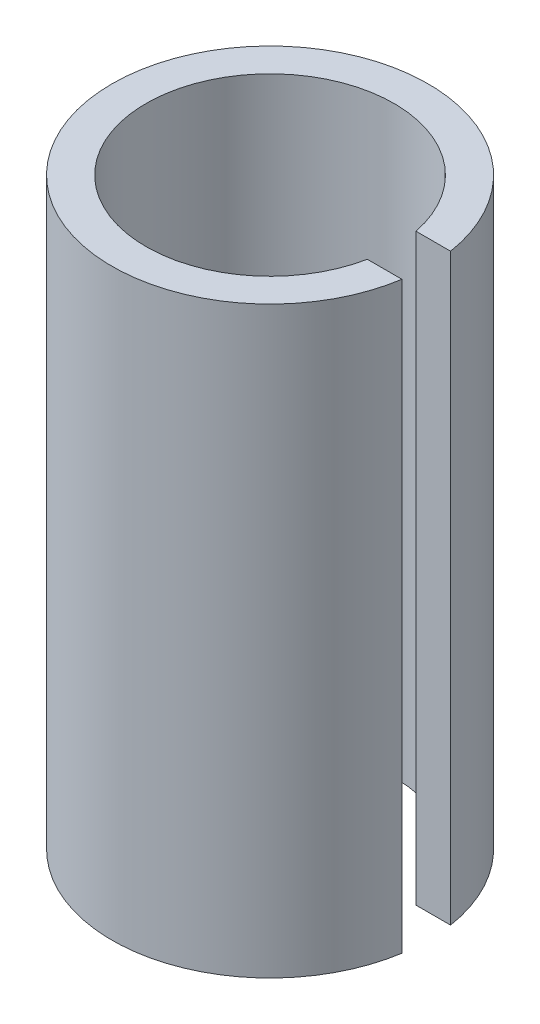
SolidWorks part; units mm, degrees
ref_plane "Front Plane" through (0, 0, 0) normal (0, 0, 1) x (1, 0, 0)
ref_plane "Top Plane" through (0, 0, 0) normal (0, 1, 0) x (1, 0, 0)
ref_plane "Right Plane" through (0, 0, 0) normal (1, 0, 0) x (0, 0, -1)
sketch "Sketch1" plane through (0, 0, 0) normal (0, 1, 0) x (1, 0, 0)
  line L0 (2.5005, 0.5) -> (3.2113, 0.5)
  line L1 (2.5005, -0.5) -> (3.2113, -0.5)
  line L2 (0, 0) -> (3.25, 0) construction
  circle A0 centre (0, 0) radius 3.25
  circle A1 centre (0, 0) radius 2.55
  dimension "D1" = 5.1
  dimension "D2" = 6.5
  dimension "D3" = 1
  dimension "D4" = 0.5
extrude "Boss-Extrude1" add sketch "Sketch1" along normal blind 12 contours A1 L0 A0 L1 region at (-2.6417, 0, 0)
